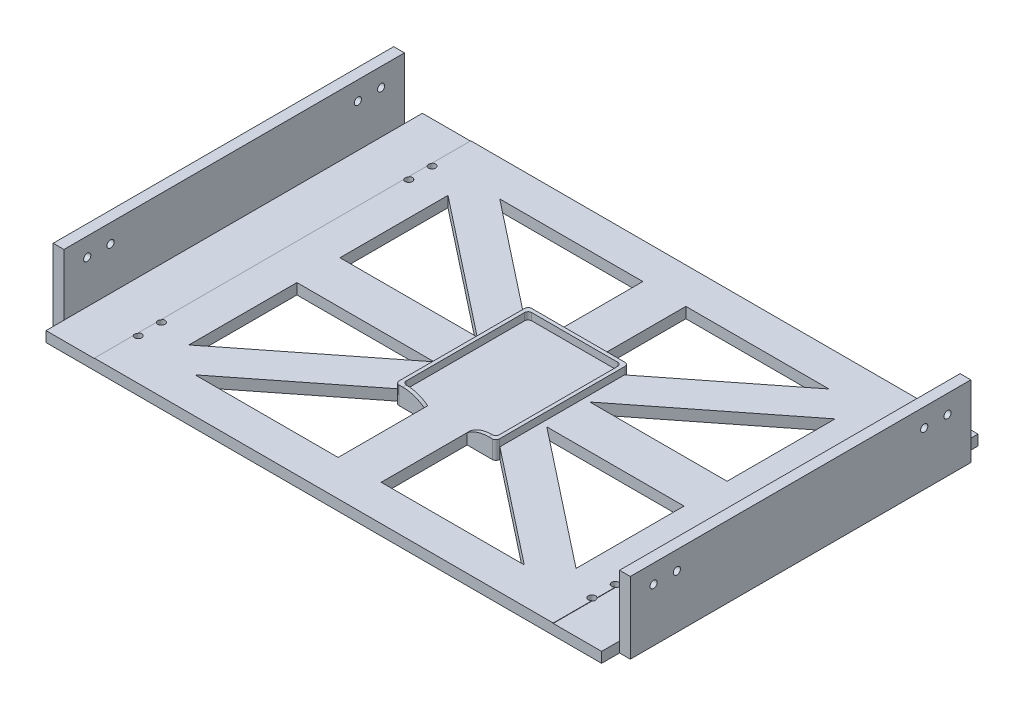
SolidWorks part; units mm, degrees
ref_plane "Front Plane" through (0, 0, 0) normal (0, 0, 1) x (1, 0, 0)
ref_plane "Top Plane" through (0, 0, 0) normal (0, 1, 0) x (1, 0, 0)
ref_plane "Right Plane" through (0, 0, 0) normal (1, 0, 0) x (0, 0, -1)
sketch "Sketch1" plane through (0, 0, 0) normal (0, 1, 0) x (1, 0, 0)
  line L1 (-77.5, -52.5) -> (77.5, -52.5)
  line L2 (-77.5, -52.5) -> (-77.5, 52.5)
  line L3 (-77.5, 52.5) -> (77.5, 52.5)
  line L4 (77.5, -52.5) -> (77.5, 52.5)
  line L5 (-77.5, -52.5) -> (77.5, 52.5) construction
  line L6 (-77.5, 52.5) -> (77.5, -52.5) construction
  line L7 (-77.5, -52.5) -> (-64, -52.5)
  line L8 (-77.5, -52.5) -> (-77.5, 52.5)
  line L9 (-77.5, 52.5) -> (-64, 52.5)
  line L10 (-64, -52.5) -> (-64, 52.5)
  line L11 (77.5, -52.5) -> (64, -52.5)
  line L12 (77.5, -52.5) -> (77.5, 52.5)
  line L13 (77.5, 52.5) -> (64, 52.5)
  line L14 (64, -52.5) -> (64, 52.5)
  point P0 (0, 0)
  dimension "D1" = 155
  dimension "D2" = 105
  dimension "D3" = 13.5
  dimension "D4" = 13.5
extrude "Boss-Extrude1" add sketch "Sketch1" along normal blind 3 contours L1 L14 L3 L10 region at (0, 0, 0)
sketch "Sketch2" plane through (0, 0, 0) normal (0, 1, 0) x (1, 0, 0)
  line L0 (-64, 52.5) -> (64, 52.5) construction
  line L1 (-64, 52.5) -> (-77.5, 52.5)
  line L2 (-64, 52.5) -> (-64, -52.5)
  line L3 (-64, -52.5) -> (-77.5, -52.5)
  line L4 (-77.5, 52.5) -> (-77.5, -52.5)
  line L5 (64, -52.5) -> (77.5, -52.5)
  line L6 (64, -52.5) -> (64, 52.5)
  line L7 (64, 52.5) -> (77.5, 52.5)
  line L8 (77.5, -52.5) -> (77.5, 52.5)
  dimension "D1" = 105
  dimension "D2" = 105
  dimension "D3" = 13.5
  dimension "D4" = 13.5
extrude "Boss-Extrude2" add sketch "Sketch2" along normal blind 2.9
sketch "Sketch3" plane through (0, 0, 0) normal (0, 1, 0) x (1, 0, 0)
  line L0 (-77.5, 52.5) -> (-77.5, -52.5) construction
  line L1 (-77.5, 47.5) -> (-80.5, 47.5)
  line L2 (-77.5, 47.5) -> (-77.5, -47.5)
  line L3 (-77.5, -47.5) -> (-80.5, -47.5)
  line L4 (-80.5, 47.5) -> (-80.5, -47.5)
  line L5 (77.5, -52.5) -> (77.5, 52.5) construction
  line L6 (77.5, -47.5) -> (80.5, -47.5)
  line L7 (77.5, -47.5) -> (77.5, 47.5)
  line L8 (77.5, 47.5) -> (80.5, 47.5)
  line L9 (80.5, -47.5) -> (80.5, 47.5)
  line L10 (-77.5, -52.5) -> (-64, -52.5) construction
  dimension "D1" = 95
  dimension "D2" = 5
  dimension "D3" = 0
  dimension "D4" = 0
  dimension "D5" = 3
  dimension "D6" = 3
sketch "Sketch5" plane through (0, 3, 0) normal (0, 1, 0) x (1, 0, 0)
  line L0 (-6, -17.5) -> (-6, -18.5)
  line L1 (-13, -17.5) -> (13, -17.5)
  line L2 (-13, -17.5) -> (-13, 17.5)
  line L3 (-13, 17.5) -> (13, 17.5)
  line L4 (13, -17.5) -> (13, 17.5)
  line L5 (-13, -17.5) -> (13, 17.5) construction
  line L6 (-13, 17.5) -> (13, -17.5) construction
  line L7 (-14, -18.5) -> (14, -18.5)
  line L8 (-14, -18.5) -> (-14, 18.5)
  line L9 (-14, 18.5) -> (14, 18.5)
  line L10 (14, -18.5) -> (14, 18.5)
  line L11 (-14, -18.5) -> (14, 18.5) construction
  line L12 (-14, 18.5) -> (14, -18.5) construction
  line L13 (6, -17.5) -> (6, -18.5)
  line L14 (0, 0) -> (0, -10.4966)
  point P0 (0, 0)
  point P6 (0, 0)
  dimension "D1" = 26
  dimension "D2" = 35
  dimension "D3" = 1
  dimension "D4" = 1
  dimension "D5" = 8
extrude "Boss-Extrude9" add sketch "Sketch5" along normal blind 7 contours L1 L13 L7 L10 L9 L8 L0 L2 L3 L4 region at (-6.464, 3, 18)
fillet "Fillet2" radius 1 8 edges at (-13, 6.5, 17.5) (13, 6.5, 17.5) (-13, 6.5, -17.5) (14, 6.5, -18.5) (14, 6.5, 18.5) (13, 6.5, -17.5) (-14, 6.5, -18.5) (-14, 6.5, 18.5)
sketch "Sketch10" plane through (0, 3, 0) normal (0, 1, 0) x (1, 0, 0)
  line L0 (-64, -52.5) -> (-64, 52.5) construction
  line L1 (-54, -42.5) -> (54, -42.5)
  line L2 (-54, -42.5) -> (-54, 42.5)
  line L3 (-54, 42.5) -> (54, 42.5)
  line L4 (54, -42.5) -> (54, 42.5)
  line L5 (-54, -42.5) -> (54, 42.5) construction
  line L6 (-54, 42.5) -> (54, -42.5) construction
  line L7 (-64, 52.5) -> (64, 52.5) construction
  line L8 (-54, 36.1372) -> (45.9155, -42.5)
  line L9 (-45.9155, -42.5) -> (54, 36.1372)
  line L10 (-54, -36.1372) -> (45.9155, 42.5)
  line L11 (-45.9155, 42.5) -> (54, -36.1372)
  line L12 (-6, -18.5) -> (6, -18.5)
  line L13 (-54, -6) -> (54, -6)
  line L14 (-54, -6) -> (-54, 6)
  line L15 (-54, 6) -> (54, 6)
  line L16 (54, -6) -> (54, 6)
  line L17 (-54, -6) -> (54, 6) construction
  line L18 (-54, 6) -> (54, -6) construction
  line L19 (-6, 42.5) -> (6, 42.5)
  line L20 (-6, 42.5) -> (-6, -42.5)
  line L21 (-6, -42.5) -> (6, -42.5)
  line L22 (6, 42.5) -> (6, -42.5)
  line L23 (-6, 42.5) -> (6, -42.5) construction
  line L24 (-6, -42.5) -> (6, 42.5) construction
  point P0 (0, 0)
  point P18 (0, 0)
  point P23 (0, 0)
  line M19 (-6, -18.5) -> (-13, -18.5)
  arc M20 (-13, -18.5) -> (-14, -17.5) centre (-13, -17.5) cw
  line M21 (-14, -17.5) -> (-14, 17.5)
  arc M22 (-14, 17.5) -> (-13, 18.5) centre (-13, 17.5) cw
  line M23 (-13, 18.5) -> (13, 18.5)
  arc M24 (13, 18.5) -> (14, 17.5) centre (13, 17.5) cw
  line M25 (14, 17.5) -> (14, -17.5)
  arc M26 (14, -17.5) -> (13, -18.5) centre (13, -17.5) cw
  line M27 (13, -18.5) -> (6, -18.5)
  dimension "D1" = 10
  dimension "D2" = 10
  dimension "D3" = 5
  dimension "D4" = 5
  dimension "D5" = 10
  dimension "D6" = 10
  dimension "D7" = 12
  dimension "D8" = 12
extrude "Cut-Extrude1" cut sketch "Sketch10" against normal blind 7 contours L2 L15 L8 | L20 L3 L11 M21 M22 M23 | L3 L22 L10 M23 M24 M25 | L9 L15 L4 | L13 L11 L4 | L12 L22 L1 L8 M25 M26 M27 | L20 L12 L9 L1 M19 M20 M21 | L13 L2 L10 region at (-19.8954, 3, 32.9471) region at (-41.236, 3, 16.0457) region at (19.8954, 3, 32.9471) region at (-41.236, 3, -16.0457) region at (41.236, 3, 16.0457) region at (-19.8954, 3, -32.9471) region at (41.236, 3, -16.0457) region at (19.8954, 3, -32.9471)
extrude "Boss-Extrude10" add sketch "Sketch3" along normal blind 20
sketch "Sketch11" plane through (0, 3, 0) normal (0, 1, 0) x (1, 0, 0)
  line L0 (-64, -52.5) -> (-64, -42.5)
  line L1 (-64, -52.5) -> (-64, 52.5) construction
  line L2 (-64, -42.5) -> (-63.3, -42.5)
  line L3 (-63.3, -39.5) -> (-63.3, -36)
  line L4 (-63.3, -33) -> (-64, -33)
  line L5 (0, 0) -> (29.0728, 0) construction
  line L6 (29.0728, 0) -> (0, 0) construction
  line L7 (0, 0) -> (0, 24.7559) construction
  line L8 (-63.3, 33) -> (-64, 33)
  line L9 (-63.3, 39.5) -> (-63.3, 36)
  line L10 (-64, 42.5) -> (-63.3, 42.5)
  line L11 (64, 42.5) -> (63.3, 42.5)
  line L12 (63.3, 39.5) -> (63.3, 36)
  line L13 (63.3, 33) -> (64, 33)
  line L14 (63.3, -33) -> (64, -33)
  line L15 (63.3, -39.5) -> (63.3, -36)
  line L16 (64, -42.5) -> (63.3, -42.5)
  arc A0 (-63.3, -42.5) -> (-63.3, -39.5) centre (-63.3, -41) ccw
  circle A1 centre (-63.3, -41) radius 1
  arc A2 (-63.3, -36) -> (-63.3, -33) centre (-63.3, -34.5) ccw
  circle A3 centre (-63.3, -34.5) radius 1
  circle A4 centre (-63.3, 34.5) radius 1
  arc A5 (-63.3, 36) -> (-63.3, 33) centre (-63.3, 34.5) cw
  circle A6 centre (-63.3, 41) radius 1
  arc A7 (-63.3, 42.5) -> (-63.3, 39.5) centre (-63.3, 41) cw
  arc A8 (63.3, 42.5) -> (63.3, 39.5) centre (63.3, 41) ccw
  circle A9 centre (63.3, 41) radius 1
  arc A10 (63.3, 36) -> (63.3, 33) centre (63.3, 34.5) ccw
  circle A11 centre (63.3, 34.5) radius 1
  circle A12 centre (63.3, -34.5) radius 1
  arc A13 (63.3, -36) -> (63.3, -33) centre (63.3, -34.5) cw
  circle A14 centre (63.3, -41) radius 1
  arc A15 (63.3, -42.5) -> (63.3, -39.5) centre (63.3, -41) cw
  dimension "D3" = 1.5
  dimension "D4" = 2
  dimension "D6" = 1.5
  dimension "D7" = 2
  dimension "D1" = 10
  dimension "D2" = 0.7
  dimension "D5" = 3.5
  dimension "D8" = 6.5
extrude "Cut-Extrude2" cut sketch "Sketch11" against normal blind 20 contours A1 | A3 | A6 | A4 | A9 | A11 | A14 | A12
sketch "Sketch13" plane through (-77.5, 0, 0) normal (1, 0, 0) x (0, 0, -1)
  line L0 (-42.5, 14.8425) -> (-39.5, 14.8425)
  line L1 (-52.5, 2.9) -> (-42.5, 2.9)
  line L2 (-42.5, 2.6425) -> (-42.5, 14.8425)
  line L4 (-39.5, 14.8425) -> (-36, 14.8425)
  arc A0 (-42.5, 14.8425) -> (-39.5, 14.8425) centre (-41, 14.8425) cw
  circle A1 centre (-41, 14.8425) radius 1
  arc A2 (-36, 14.8425) -> (-33, 14.8425) centre (-34.5, 14.8425) cw
  circle A3 centre (-34.5, 14.8425) radius 1
  dimension "D3" = 1.5
  dimension "D4" = 2
  dimension "D6" = 1.5
  dimension "D7" = 2
  dimension "D1" = 10
  dimension "D2" = 12.2
  dimension "D5" = 3.5
extrude "Cut-Extrude3" cut sketch "Sketch13" against normal blind 20 contours A1 | A3
mirror "Mirror1" about plane through (0, 0, 0) normal (0, 0, 1) of "Cut-Extrude3" second plane through (0, 0, 0) second plane normal (1, 0, 0)
ref_plane "Plane1" through (-77.5, 0, 47.5) normal (1, 0, 0) x (0, 0, -1)
sketch "Sketch22" plane through (0, 10, 0) normal (0, 1, 0) x (1, 0, 0)
  line L12 (14, -17.5) -> (14, 17.5)
  line L13 (13, 18.5) -> (-13, 18.5)
  line L14 (-14, 17.5) -> (-14, -17.5)
  line L15 (-13, -18.5) -> (-6, -18.5)
  line L16 (-6, -18.5) -> (-6, -17.5)
  line L17 (-6, -17.5) -> (-12, -17.5)
  line L18 (-13, -16.5) -> (-13, 16.5)
  line L19 (-12, 17.5) -> (12, 17.5)
  line L20 (13, 16.5) -> (13, -16.5)
  line L21 (12, -17.5) -> (6, -17.5)
  line L22 (6, -17.5) -> (6, -18.5)
  line L23 (6, -18.5) -> (13, -18.5)
  line L24 (14, -17.5) -> (14, 17.5)
  line L25 (13, 18.5) -> (-13, 18.5)
  line L26 (-14, 17.5) -> (-14, -17.5)
  line L27 (-13, -18.5) -> (-6, -18.5)
  line L28 (-6, -18.5) -> (-6, -17.5)
  line L29 (-6, -17.5) -> (-12, -17.5)
  line L30 (-13, -16.5) -> (-13, 16.5)
  line L31 (-12, 17.5) -> (12, 17.5)
  line L32 (13, 16.5) -> (13, -16.5)
  line L33 (12, -17.5) -> (6, -17.5)
  line L34 (6, -17.5) -> (6, -18.5)
  line L35 (6, -18.5) -> (13, -18.5)
  arc A8 (14, 17.5) -> (13, 18.5) centre (13, 17.5) ccw
  arc A9 (-13, 18.5) -> (-14, 17.5) centre (-13, 17.5) ccw
  arc A10 (-14, -17.5) -> (-13, -18.5) centre (-13, -17.5) ccw
  arc A11 (-13, -16.5) -> (-12, -17.5) centre (-12, -16.5) ccw
  arc A12 (-12, 17.5) -> (-13, 16.5) centre (-12, 16.5) ccw
  arc A13 (13, 16.5) -> (12, 17.5) centre (12, 16.5) ccw
  arc A14 (12, -17.5) -> (13, -16.5) centre (12, -16.5) ccw
  arc A15 (13, -18.5) -> (14, -17.5) centre (13, -17.5) ccw
  arc A16 (14, 17.5) -> (13, 18.5) centre (13, 17.5) ccw
  arc A17 (-13, 18.5) -> (-14, 17.5) centre (-13, 17.5) ccw
  arc A18 (-14, -17.5) -> (-13, -18.5) centre (-13, -17.5) ccw
  arc A19 (-13, -16.5) -> (-12, -17.5) centre (-12, -16.5) ccw
  arc A20 (-12, 17.5) -> (-13, 16.5) centre (-12, 16.5) ccw
  arc A21 (13, 16.5) -> (12, 17.5) centre (12, 16.5) ccw
  arc A22 (12, -17.5) -> (13, -16.5) centre (12, -16.5) ccw
  arc A23 (13, -18.5) -> (14, -17.5) centre (13, -17.5) ccw
  dimension "D1" = 0
extrude "Cut-Extrude8" cut sketch "Sketch22" against normal blind 5
fillet "Fillet3" radius 10 2 edges at (6, 5, 18) (-6, 5, 18)
